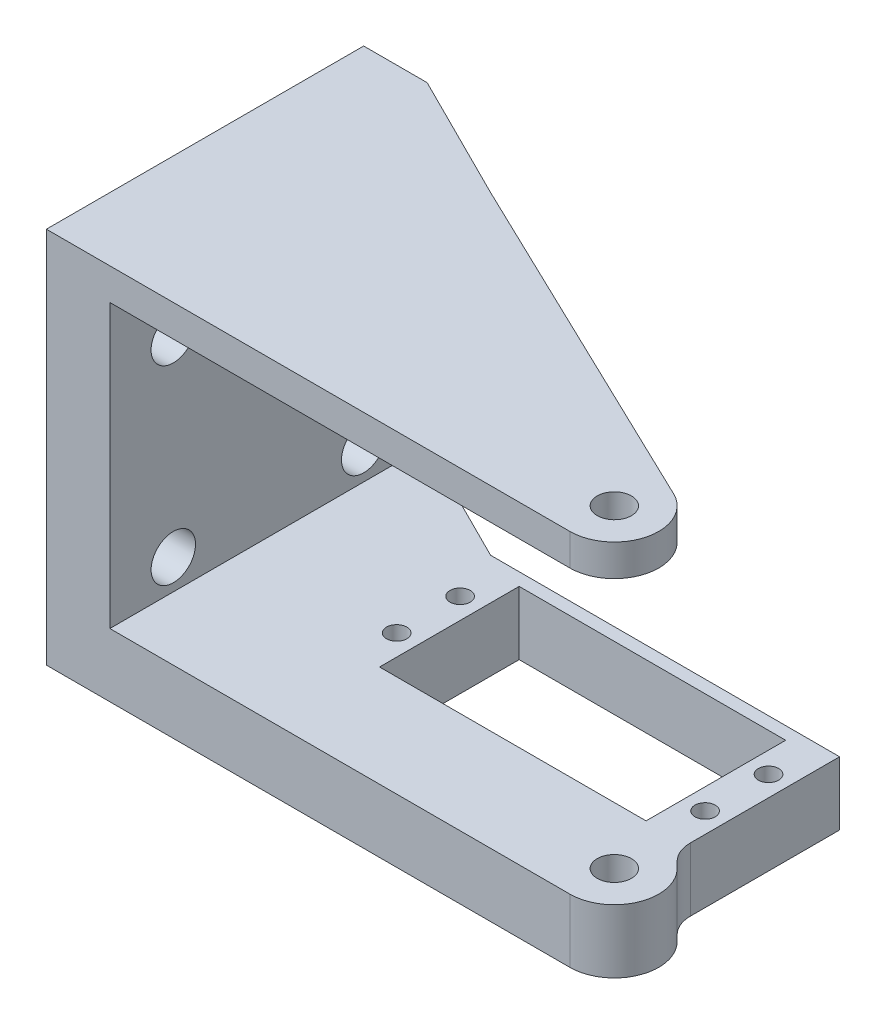
SolidWorks part; units mm, degrees
material "ABS"
ref_plane "Front Plane" through (0, 0, 0) normal (0, 0, 1) x (1, 0, 0)
ref_plane "Top Plane" through (0, 0, 0) normal (0, 1, 0) x (1, 0, 0)
ref_plane "Right Plane" through (0, 0, 0) normal (1, 0, 0) x (0, 0, -1)
ref_axis "X" through (-88.99, 0, 0) along (1, 0, 0)
ref_axis "Y" through (0, 55, 0) along (0, -1, 0)
ref_axis "Z" through (0, 0, -88.99) along (0, 0, 1)
sketch "Sketch1" plane through (0, 0, 0) normal (0, 1, 0) x (1, 0, 0)
  line L0 (4.9497, 4.9497) -> (3.9645, 5.935)
  line L1 (2.5, 9.4706) -> (2.5, 33)
  line L2 (2.5, 33) -> (-52.5, 33)
  line L3 (-52.5, 33) -> (-52.5, -7)
  line L4 (0, -7) -> (-52.5, -7)
  line L5 (-25, 20) -> (-25, 33) construction
  line L6 (-49.3, 25) -> (-0.7, 25) construction
  line L7 (-49.3, 25) -> (-49.3, 15) construction
  line L8 (-49.3, 15) -> (-0.7, 15) construction
  line L9 (-0.7, 25) -> (-0.7, 15) construction
  line L10 (-49.3, 25) -> (-0.7, 15) construction
  line L11 (-49.3, 15) -> (-0.7, 25) construction
  line L12 (-52.5, -7) -> (-82.5, -7)
  line L13 (-46, 31) -> (-4, 31)
  line L14 (-46, 31) -> (-46, 9)
  line L15 (-46, 9) -> (-4, 9)
  line L16 (-4, 31) -> (-4, 9)
  line L17 (-46, 31) -> (-4, 9) construction
  line L18 (-46, 9) -> (-4, 31) construction
  line L19 (-72.5, 43) -> (-82.5, 43)
  line L20 (-72.5, 43) -> (-52.5, 33)
  line L21 (-82.5, 43) -> (-82.5, -7)
  line L22 (-72.5, 43) -> (-72.5, -7)
  circle A0 centre (0, 0) radius 5
  arc A1 (0, -7) -> (4.9497, 4.9497) centre (0, 0) ccw
  arc A2 (3.9645, 5.935) -> (2.5, 9.4706) centre (7.5, 9.4706) cw
  circle A3 centre (-0.7, 25) radius 1.6
  circle A4 centre (-0.7, 15) radius 1.6
  circle A5 centre (-49.3, 15) radius 1.6
  circle A6 centre (-49.3, 25) radius 1.6
  point P18 (-25, 20)
  dimension "D1" = 10
  dimension "D2" = 45
  dimension "D3" = 2
  dimension "D4" = 5
  dimension "D5" = 3.2
  dimension "D6" = 42
  dimension "D7" = 22
  dimension "D8" = 48.6
  dimension "D9" = 10
  dimension "D10" = 25
  dimension "D11" = 20
  dimension "D12" = 55
  dimension "D13" = 2
  dimension "D14" = 50
  dimension "D15" = 10
  dimension "D16" = 20
extrude "Boss-Extrude1" add sketch "Sketch1" against normal blind 10 contours L0 A2 L1 L2 L3 L4 A1 A6 A5 A4 A3 L13 L16 L15 L14 A0 region at (-25.5649, 0, -7.8484)
extrude "Boss-Extrude2" add sketch "Sketch1<4>" against normal up to surface (10 mm away) contours L20 L22 L12 L3 region at (-62.8704, 0, -15.5926) up to face at (-49.3, -10, -23.4)
sketch "Sketch1<4>" plane through (0, 0, 0) normal (0, 1, 0) x (1, 0, 0) same geometry as "Sketch1"
sketch "Sketch2" plane through (0, 0, 0) normal (0, 1, 0) x (1, 0, 0)
  line L0 (-72.5, 43) -> (-52.5, 33) construction
  line L4 (0, -7) -> (-52.5, -7) construction
  line L5 (-52.5, -7) -> (-82.5, -7) construction
  line L6 (-82.5, 43) -> (-82.5, -7) construction
  line L7 (-72.5, 43) -> (-82.5, 43) construction
  line L8 (-72.5, 43) -> (-52.5, 33)
  line L12 (0, -7) -> (-52.5, -7)
  line L13 (-52.5, -7) -> (-82.5, -7)
  line L14 (-82.5, 43) -> (-82.5, -7)
  line L15 (-72.5, 43) -> (-82.5, 43)
  line L16 (-52.5, 33) -> (3.0324, 6.3091)
  circle A1 centre (0, 0) radius 5 construction
  arc A2 (0, -7) -> (4.9497, 4.9497) centre (0, 0) ccw construction
  circle A4 centre (0, 0) radius 5
  arc A5 (0, -7) -> (3.0324, 6.3091) centre (0, 0) ccw
ref_plane "Plane1" through (0, 44.5, 0) normal (0, 1, 0) x (1, 0, 0)
extrude "Boss-Extrude4" add sketch "Sketch2" along normal blind 5 from surface separate body starting at plane "Plane1"
extrude "Boss-Extrude3" add sketch "Sketch1<5>" against normal up to surface (10 mm away) and the other way up to surface (44.5 mm away) contours L22 L19 L21 L12 region at (-77.5, 0, -18) up to face at (-49.3, -10, -23.4) other way up to plane "Plane1"
sketch "Sketch1<5>" plane through (0, 0, 0) normal (0, 1, 0) x (1, 0, 0) same geometry as "Sketch1"
sketch "Sketch3" plane through (-82.5, 0, 0) normal (-1, 0, 0) x (0, 0, 1)
  line L0 (7, 19.75) -> (-3, 19.75) construction
  line L1 (-33, 34.75) -> (-3, 34.75) construction
  line L2 (-33, 34.75) -> (-33, 4.75) construction
  line L3 (-33, 4.75) -> (-3, 4.75) construction
  line L4 (-3, 34.75) -> (-3, 4.75) construction
  line L5 (-33, 34.75) -> (-3, 4.75) construction
  line L6 (-33, 4.75) -> (-3, 34.75) construction
  line L7 (-18, 49.5) -> (-18, 34.75) construction
  line L10 (-43, -10) -> (7, -10)
  line L11 (7, -10) -> (7, 49.5)
  line L12 (7, 49.5) -> (-43, 49.5)
  line L13 (-43, 49.5) -> (-43, -10)
  line L14 (-43, -10) -> (7, -10) construction
  line L15 (7, -10) -> (7, 49.5) construction
  line L16 (7, 49.5) -> (-43, 49.5) construction
  line L17 (-43, 49.5) -> (-43, -10) construction
  circle A0 centre (-3, 34.75) radius 3.5
  circle A1 centre (-3, 4.75) radius 3.5
  circle A2 centre (-33, 4.75) radius 3.5
  circle A3 centre (-33, 34.75) radius 3.5
  point P0 (-18, 19.75)
  dimension "D3" = 7
  dimension "D1" = 30
  dimension "D2" = 0
extrude "Cut-Extrude1" cut sketch "Sketch3" against normal up to surface (10 mm away) up to face at (-72.5, 22.25, -18)
sketch "Sketch4" plane through (0, 0, 0) normal (0, 1, 0) x (1, 0, 0)
  circle A0 centre (0, 0) radius 5 construction
  circle A1 centre (0, 0) radius 5
  circle A2 centre (0, 0) radius 2.7
  dimension "D1" = 5.4
extrude "Boss-Extrude5" add sketch "Sketch4" against normal up to surface (10 mm away) up to face at (-49.3, -10, -23.4)
extrude "Boss-Extrude6" add sketch "Sketch4<2>" along normal up to surface (49.5 mm away) from surface up to face at (-46.9431, 49.5, -18.3499) starting at face at (-37.8317, 44.5, -13.4199)
sketch "Sketch4<2>" plane through (0, 0, 0) normal (0, 1, 0) x (1, 0, 0) same geometry as "Sketch4"
